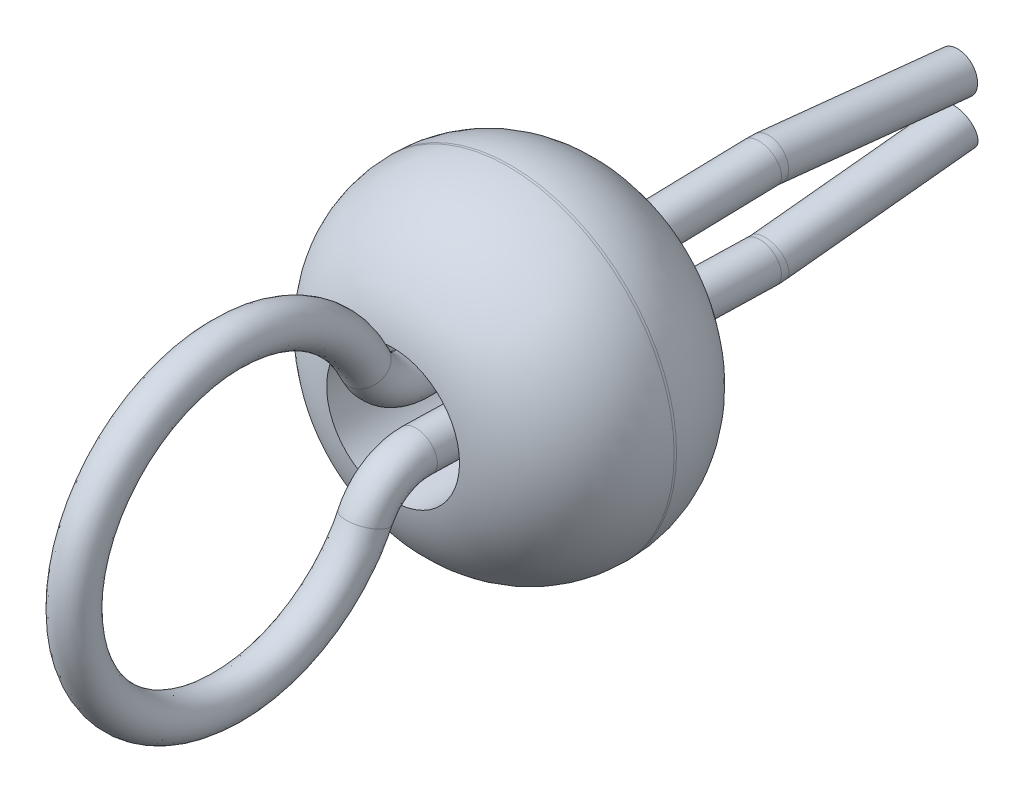
SolidWorks part; units mm, degrees
ref_plane "Front Plane" through (0, 0, 0) normal (0, 0, 1) x (1, 0, 0)
ref_plane "Top Plane" through (0, 0, 0) normal (0, 1, 0) x (1, 0, 0)
ref_plane "Right Plane" through (0, 0, 0) normal (1, 0, 0) x (0, 0, -1)
sketch "Sketch1" plane through (0, 0, 0) normal (0, 0, 1) x (1, 0, 0)
  circle A0 centre (0, 0) radius 1.27
  circle A1 centre (0, 0) radius 0.508
  dimension "D1" = 2.54
  dimension "D2" = 0.762
extrude "Plastic-Ring" add sketch "Sketch1" along normal blind 1.778
sketch "wire-bend" plane through (0, 0, 0) normal (1, 0, 0) x (0, 0, -1)
  line L0 (-5.3581, 0) -> (4.6063, 0) construction
  line L1 (1.039, -0.3295) -> (-1.5921, -0.262)
  line L2 (2.54, 0.1778) -> (1.0945, 0.3273)
  line L4 (1.039, 0.3295) -> (-1.5921, 0.262)
  line L7 (2.54, -0.1778) -> (1.0945, -0.3273)
  arc A0 (-1.9925, 0.5068) -> (-1.9925, -0.5068) centre (-3.048, 0) ccw
  arc A1 (-1.5921, 0.262) -> (-1.9925, 0.5068) centre (-1.6032, 0.6937) cw
  arc A2 (1.0945, 0.3273) -> (1.039, 0.3295) centre (1.05, -0.1022) ccw
  arc A3 (1.0945, -0.3273) -> (1.039, -0.3295) centre (1.05, 0.1022) cw
  arc A4 (-1.5921, -0.262) -> (-1.9925, -0.5068) centre (-1.6032, -0.6937) ccw
  point P12 (-1.905, 0.254)
  point P15 (1.0668, 0.3302)
  point P23 (1.0668, -0.3302)
  point P24 (-1.905, -0.254)
  dimension "D2" = 0.4318
  dimension "D1" = 3.048
  dimension "D3" = 0.1778
  dimension "D4" = 2.54
  dimension "D5" = 1.0668
  dimension "D6" = 0.3302
  dimension "D7" = 0.254
  dimension "D8" = 1.905
ref_plane "Plane1" through (0, 0, -2.54) normal (0, 0, 1) x (1, 0, 0)
sketch "wire-profile" plane through (0, 0, -2.54) normal (0, 0, 1) x (1, 0, 0)
  circle A4 centre (0, 0.1778) radius 0.1524
  point P0 (0, 0.1778)
sweep "Sweep3" add profiles "wire-profile" path "wire-bend"
ref_plane "Plane2" through (0, 0, -1.5748) normal (0, 0, 1) x (1, 0, 0)
sketch "VIA hole" plane through (0, 0, -1.5748) normal (0, 0, 1) x (1, 0, 0)
  circle A0 centre (0, 0) radius 0.508 construction
  circle A1 centre (0, 0) radius 0.5334 construction
  dimension "D1" = 1.016
  dimension "D2" = 0.0254
fillet "圆角6" radius 0.889 2 edges at (1.27, 0, 0) (1.27, 0, 1.778)
